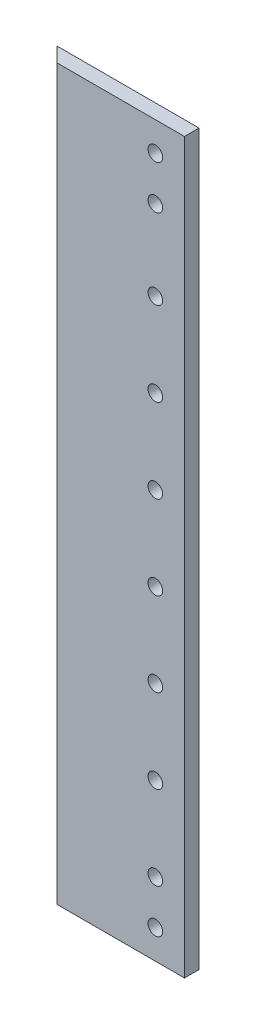
SolidWorks part; units mm, degrees
ref_plane "Front Plane" through (0, 0, 0) normal (0, 0, 1) x (1, 0, 0)
ref_plane "Top Plane" through (0, 0, 0) normal (0, 1, 0) x (1, 0, 0)
ref_plane "Right Plane" through (0, 0, 0) normal (1, 0, 0) x (0, 0, -1)
sketch "Sketch1" plane through (0, 0, 0) normal (0, 0, 1) x (1, 0, 0)
  line L1 (-40, 200) -> (0, 200)
  line L2 (-40, 200) -> (-40, 0)
  line L3 (-40, 0) -> (0, 0)
  line L4 (0, 200) -> (0, 0)
  dimension "D1" = 40
  dimension "D2" = 200
extrude "Boss-Extrude1" add sketch "Sketch1" along normal blind 4
sketch "Sketch6" plane through (0, 0, 0) normal (0, 0, 1) x (1, 0, 0)
  line L0 (-40, 0) -> (0, 0) construction
  line L1 (0, 0) -> (0, 200) construction
  circle A0 centre (-8, 8) radius 2
  circle A1 centre (-8, 20) radius 2
  dimension "D1" = 4
  dimension "D2" = 8
  dimension "D3" = 12
  dimension "D4" = 8
extrude "Cut-Extrude3" cut sketch "Sketch6" along normal up to surface (4 mm away) up to face at (-20, 100, 4)
ref_plane "Plane1" through (0, 100, 0) normal (0, 1, 0) x (1, 0, 0)
mirror "Mirror1" about plane through (0, 100, 0) normal (0, 1, 0) of "Cut-Extrude3"
sketch "Sketch7" plane through (0, 0, 0) normal (0, 0, 1) x (1, 0, 0)
  line L0 (-8, 43) -> (-8, 20) construction
  circle A0 centre (-8, 43) radius 2
  dimension "D2" = 4
  dimension "D1" = 23
extrude "Cut-Extrude4" cut sketch "Sketch7" along normal up to surface (4 mm away) up to face at (-6, 192, 4)
pattern_linear "LPattern1" count 6 spacing 23 along (0, 1, 0) of "Cut-Extrude4"
sketch "Sketch3" plane through (-200, 0, 0) normal (0, 0, -1) x (-1, 0, 0)
  line L8 (-160, 0) -> (-195.2654, 0)
  line L9 (-160, 0) -> (-200, 0) construction
  line L10 (-160, 200) -> (-160, 0) construction
  line L11 (-195.2654, 0) -> (-160, 200)
  line L12 (-160, 200) -> (-160, 0)
  line L13 (-174.1062, 0) -> (-174.1062, 120) construction
  dimension "D1" = 10
  dimension "D2" = 120
extrude "傾斜刀" [suppressed] cut sketch "Sketch3" against normal up to surface (4 mm away) up to face at (-6, 66, 4)
chamfer "傾斜刀倒角" [suppressed] distance 5 angle 45
chamfer "垂直刀倒角" distance 5 angle 45 1 edges at (-40, 100, 4)
